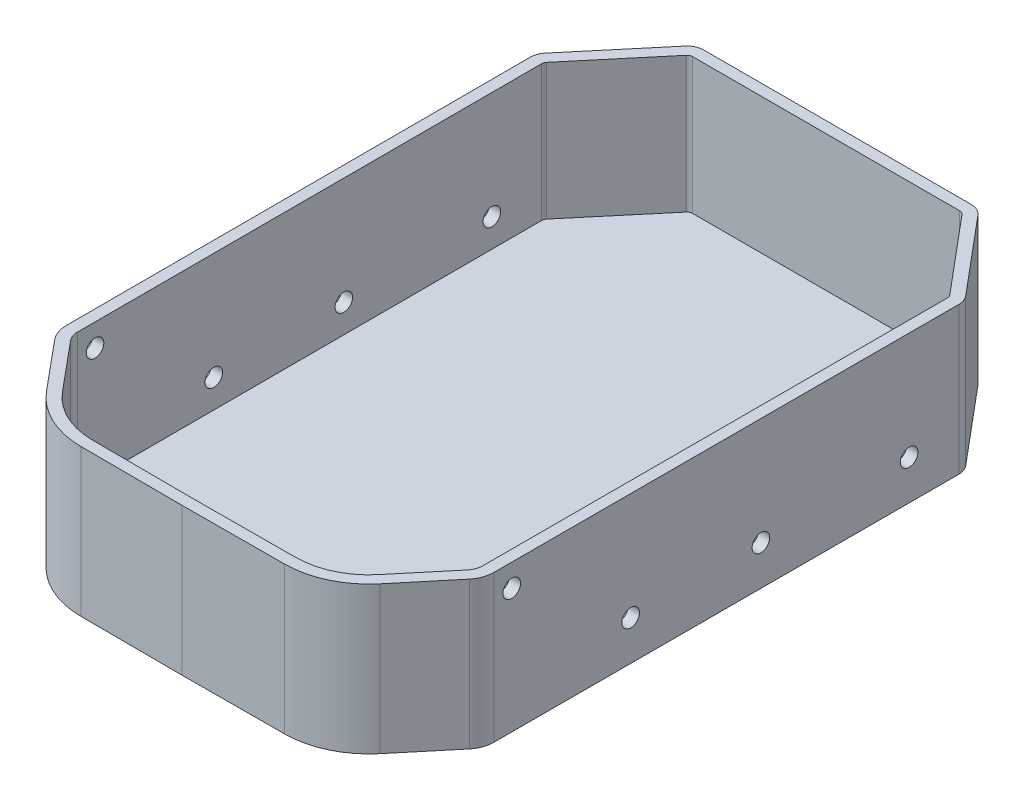
SolidWorks part; units mm, degrees
ref_plane "Ebene vorne" through (0, 0, 0) normal (0, 0, 1) x (1, 0, 0)
ref_plane "Ebene oben" through (0, 0, 0) normal (0, 1, 0) x (1, 0, 0)
ref_plane "Ebene rechts" through (0, 0, 0) normal (1, 0, 0) x (0, 0, -1)
sketch "Skizze1" plane through (0, 0, 0) normal (0, 1, 0) x (1, 0, 0)
  line L0 (-71.7828, 0) -> (65.2574, 0) construction
  line L1 (0, -55) -> (0, 55) construction
  line L2 (0, 50.8602) -> (0, -44.8504) construction
  line L4 (0, -75.745) -> (-24.9998, -75.6418)
  line L5 (-24.9998, -75.6418) -> (-37.7921, -60.2679)
  line L6 (-37.7921, -60.2679) -> (-37.8558, 24.7321)
  line L7 (-37.8558, 24.7321) -> (-25, 40.053)
  line L8 (-25, 40.053) -> (0, 40.053)
  line L9 (0, 40.053) -> (0, -75.745)
  point P2 (0, -75.7896)
  dimension "D1" = 85
  dimension "D2" = 20
  dimension "D3" = 130
  dimension "D4" = 25
  dimension "D5" = 130
  dimension "D6" = 115.798
extrude "Aufsatz-Linear austragen1" add sketch "Skizze1" along normal blind 26
mirror "Spiegeln1" about plane through (0, 0, 0) normal (1, 0, 0) of "Aufsatz-Linear austragen1"
fillet "Verrundung11" radius 15 2 edges at (-24.9998, 13, 75.6418) (24.9998, 13, 75.6418)
fillet "Verrundung12" radius 5 2 edges at (37.7921, 13, 60.2679) (-37.7921, 13, 60.2679)
fillet "Verrundung13" radius 3 2 edges at (-25, 13, -40.053) (25, 13, -40.053)
fillet "Verrundung14" radius 3 2 edges at (37.8558, 13, -24.7321) (-37.8558, 13, -24.7321)
shell "Wandung4" thickness 2 removed face at (0, 26, 20.7928)
sketch "Skizze7" plane through (-37.8372, 0, 0.0283) normal (-1, 0, 0.0007) x (0.0007, 0, 1)
  line L0 (-23.6673, 26) -> (-23.6673, 0) construction
  line L1 (41.6413, 0) -> (-41.6413, 0) construction
  circle A0 centre (-14.8473, 7) radius 1.55
  circle A2 centre (11.3327, 7) radius 1.55
  circle A3 centre (34.3327, 7) radius 1.55
  circle A4 centre (55.3327, 22) radius 1.55
  point P6 (0, 0)
  point P7 (24.0436, -5.0437)
  point P12 (5.7117, 7)
  point P13 (30.1543, 7)
  dimension "D1" = 8.82
  dimension "D2" = 3.1
  dimension "D3" = 7
  dimension "D4" = 26.18
  dimension "D5" = 23
  dimension "D6" = 21
  dimension "D7" = 15
extrude "Schnitt-Linear austragen1" cut sketch "Skizze7" against normal up to surface (75.6944 mm away) up to face at (37.8242, 13, 17.4114)
